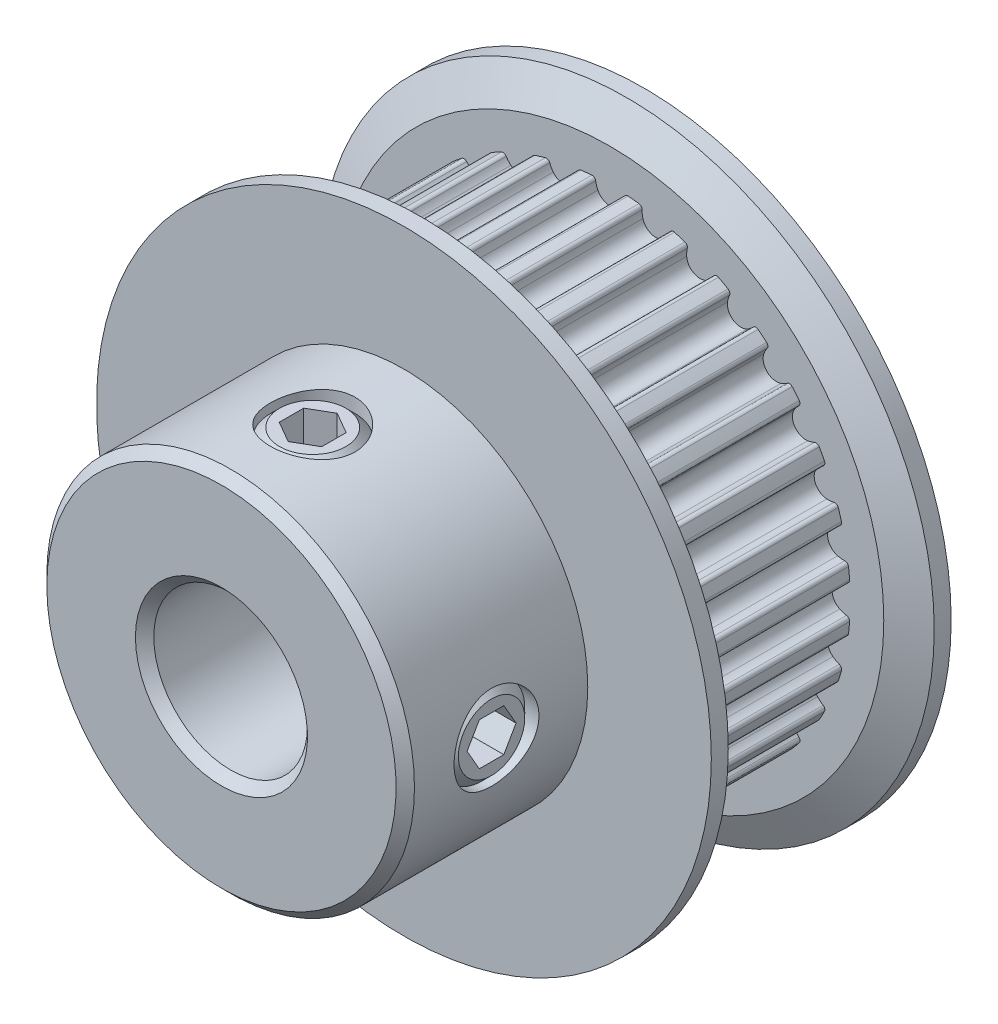
SolidWorks part; units mm, degrees
ref_plane "Front Plane" through (0, 0, 0) normal (0, 0, 1) x (1, 0, 0)
ref_plane "Top Plane" through (0, 0, 0) normal (0, 1, 0) x (1, 0, 0)
ref_plane "Right Plane" through (0, 0, 0) normal (1, 0, 0) x (0, 0, -1)
sketch "Sketch1" plane through (0, 0, 0) normal (0, 0, 1) x (1, 0, 0)
  line L1 (-1.8294, 9.1815) -> (1.8294, 9.1815) construction
  line L4 (0, 0) -> (0, 9.1815) construction
  line L5 (0, 9.1815) -> (0, 13.0713) construction
  line L6 (0, 10.1855) -> (1.9903, 9.9891) construction
  line L7 (1.9903, 9.9891) -> (2.798, 9.8282) construction
  line L8 (1.9903, 9.9891) -> (1.8294, 9.1815) construction
  line L9 (-1.9903, 9.9891) -> (-1.8294, 9.1815) construction
  line L10 (-1.9407, 9.74) -> (-2.5305, 12.7)
  line L11 (-2.5305, 12.7) -> (2.5305, 12.7)
  line L12 (2.5305, 12.7) -> (1.9407, 9.74)
  circle A0 centre (0, 0) radius 10.1855 construction
  circle A1 centre (0, 0) radius 12.7 construction
  circle A2 centre (0, 0) radius 9.9315 construction
  arc A3 (-0.4989, 9.4933) -> (0.4989, 9.4933) centre (0, 9.7365) ccw
  arc A4 (-0.4989, 9.4933) -> (-0.588, 9.7769) centre (0.4, 9.9315) cw
  arc A5 (-1.9407, 9.74) -> (-0.7475, 9.9033) centre (0, 0) cw
  arc A6 (-0.588, 9.7769) -> (-0.7475, 9.9033) centre (-0.7362, 9.7538) ccw
  arc A7 (1.9407, 9.74) -> (0.7475, 9.9033) centre (0, 0) ccw
  arc A8 (0.588, 9.7769) -> (0.7475, 9.9033) centre (0.7362, 9.7538) cw
  arc A9 (0.4989, 9.4933) -> (0.588, 9.7769) centre (-0.4, 9.9315) ccw
  point P6 (0, 20.9083)
  point P11 (0, 10.1855)
  point P13 (0, 12.7)
  point P14 (0, 9.9315)
  dimension "D1" = 7.8371
  dimension "D2" = 2.8858
sketch "Sketch2" plane through (0, 0, 0) normal (1, 0, 0) x (0, 0, -1)
  line L0 (-8.7249, 3.175) -> (8.7249, 3.175)
  line L1 (-8.7249, 3.175) -> (-8.7249, 7.595)
  line L2 (-8.7249, 7.595) -> (-1.1851, 7.595)
  line L3 (-1.1851, 7.595) -> (-1.1851, 12.7)
  line L4 (-1.1851, 12.7) -> (0.2149, 12.7) construction
  line L5 (0.2149, 12.7) -> (0.2149, 9.9315) construction
  line L6 (0.2149, 9.9315) -> (7.3249, 9.9315)
  line L7 (7.3249, 9.9315) -> (7.3249, 12.7) construction
  line L8 (7.3249, 12.7) -> (8.7249, 12.7) construction
  line L9 (8.7249, 12.7) -> (8.7249, 3.175)
  line L10 (-8.7249, 0) -> (8.7249, 0) construction
  line L11 (8.0249, 12.7) -> (7.3249, 11.3157)
  line L12 (0.2149, 11.3157) -> (-0.4851, 12.7)
  line L13 (-1.1851, 12.7) -> (-0.4851, 12.7)
  line L14 (0.2149, 11.3157) -> (0.2149, 9.9315)
  line L15 (7.3249, 9.9315) -> (7.3249, 11.3157)
  line L16 (8.0249, 12.7) -> (8.7249, 12.7)
  arc A0 (0.2149, 11.3157) -> (-0.4851, 12.7) centre (-1.5038, 11.3157) ccw construction
  arc A1 (7.3249, 11.3157) -> (8.0249, 12.7) centre (9.0436, 11.3157) cw construction
  point P12 (0.2149, 11.3157)
  point P14 (-0.4851, 12.7)
  point P20 (7.3249, 11.3157)
  point P21 (8.0249, 12.7)
  point P25 (7.3249, 0)
  point P26 (0.2149, 0)
revolve "Revolve1" add sketch "Sketch2" angle 360 mid plane about L10
sketch "Sketch3" plane through (0, 0, 0) normal (0, 0, 1) x (1, 0, 0)
  line L6 (2.5305, 12.7) -> (-2.5305, 12.7)
  line L7 (1.9407, 9.74) -> (2.5305, 12.7)
  line L8 (-2.5305, 12.7) -> (-1.9407, 9.74)
  line L9 (2.5305, 12.7) -> (-2.5305, 12.7)
  line L10 (1.9407, 9.74) -> (2.5305, 12.7)
  line L11 (-2.5305, 12.7) -> (-1.9407, 9.74)
  arc A8 (1.9407, 9.74) -> (0.7475, 9.9033) centre (0, 0) ccw
  arc A9 (0.7475, 9.9033) -> (0.588, 9.7769) centre (0.7362, 9.7538) ccw
  arc A10 (0.4989, 9.4933) -> (0.588, 9.7769) centre (-0.4, 9.9315) ccw
  arc A11 (-0.4989, 9.4933) -> (0.4989, 9.4933) centre (0, 9.7365) ccw
  arc A12 (-0.588, 9.7769) -> (-0.4989, 9.4933) centre (0.4, 9.9315) ccw
  arc A13 (-0.588, 9.7769) -> (-0.7475, 9.9033) centre (-0.7362, 9.7538) ccw
  arc A14 (-0.7475, 9.9033) -> (-1.9407, 9.74) centre (0, 0) ccw
  arc A15 (1.9407, 9.74) -> (0.7475, 9.9033) centre (0, 0) ccw
  arc A16 (0.7475, 9.9033) -> (0.588, 9.7769) centre (0.7362, 9.7538) ccw
  arc A17 (0.4989, 9.4933) -> (0.588, 9.7769) centre (-0.4, 9.9315) ccw
  arc A18 (-0.4989, 9.4933) -> (0.4989, 9.4933) centre (0, 9.7365) ccw
  arc A19 (-0.588, 9.7769) -> (-0.4989, 9.4933) centre (0.4, 9.9315) ccw
  arc A20 (-0.588, 9.7769) -> (-0.7475, 9.9033) centre (-0.7362, 9.7538) ccw
  arc A21 (-0.7475, 9.9033) -> (-1.9407, 9.74) centre (0, 0) ccw
  dimension "D1" = 0
extrude "Cut-Extrude1" cut sketch "Sketch3" against normal up to vertex (7.3249 mm away) from vertex up to point (0, 9.9315, -7.3249) starting at point (0, 9.9315, -0.2149)
pattern_circular "CirPattern1" count 32 over 360 about axis through (0, 0, 8.7249) along (0, 0, 1) of "Cut-Extrude1"
sketch "Sketch4" plane through (0, 0, 0) normal (1, 0, 0) x (0, -1, 0)
  line L0 (0, -1.1851) -> (0, -8.7249) construction
  line L1 (-7.595, -1.1851) -> (7.595, -1.1851) construction
  line L2 (-7.595, -8.7249) -> (7.595, -8.7249) construction
  circle A0 centre (0, -4.955) radius 1.7526
extrude "Cut-Extrude2" cut sketch "Sketch4" along normal through all
ref_plane "Plane1" through (0, 0, 4.955) normal (0, 0, 1) x (1, 0, 0)
sketch "Sketch5" plane through (0, 0, 4.955) normal (0, 0, 1) x (1, 0, 0)
  line L0 (0, 0.1664) -> (0, 7.595) construction
  line L1 (3.175, -1.3716) -> (3.175, 0)
  line L2 (3.556, -1.7526) -> (7.009, -1.7526)
  line L3 (3.175, 0) -> (7.595, 0) construction
  line L4 (3.175, 0) -> (7.39, 0)
  line L5 (7.39, 0) -> (7.39, -1.3716)
  line L6 (3.556, -1.7526) -> (3.175, -1.3716)
  line L7 (7.39, -1.3716) -> (7.009, -1.7526)
  circle A0 centre (0, 0) radius 7.595 construction
  circle A1 centre (0, 0) radius 3.175 construction
  point P2 (3.175, -1.7526)
  point P11 (7.39, -1.7526)
revolve "Revolve2" add sketch "Sketch5" angle 360 mid plane about L4
sketch "Sketch6" plane through (7.39, 5.3841, 0) normal (-1, 0, 0) x (0, -1, 0)
  line L1 (5.3841, 5.9669) -> (4.5078, 5.4609)
  line L2 (4.5078, 5.4609) -> (4.5078, 4.4491)
  line L3 (4.5078, 4.4491) -> (5.3841, 3.9431)
  line L4 (5.3841, 3.9431) -> (6.2604, 4.4491)
  line L5 (6.2604, 4.4491) -> (6.2604, 5.4609)
  line L6 (6.2604, 5.4609) -> (5.3841, 5.9669)
  circle A0 centre (5.3841, 4.955) radius 0.8763 construction
  dimension "D1" = 1.7526
extrude "Cut-Extrude3" cut sketch "Sketch6" along normal blind 1.3144
pattern_circular "CirPattern2" count 2 over 90 about axis through (0, 0, 8.7249) along (0, 0, 1) of "Cut-Extrude2", "Revolve2", "Cut-Extrude3"
chamfer "Chamfer1" distance 0.3798 angle 45 2 edges at (3.175, 0, 8.7249) (7.595, 0, 8.7249)
ref_axis "Center Axis 1" through (0, 0, -8.7249) along (0, 0, 1)
ref_plane "Contact Plane 1" through (0, 0, 8.7249) normal (0, 0, 1) x (1, 0, 0)
ref_plane "Contact Plane 2" through (0, 0, -8.7249) normal (0, 0, -1) x (-1, 0, 0)
equation "\"D2@Sketch1\" = \"D1@Sketch1\"/2"
equation "\"D1@Sketch6\" = \"Set Screw@Sketch4\" / 2"
equation "\"D1@Cut-Extrude3\" = \"D1@Sketch6\"*.75"
equation "\"D1@Chamfer1\"=\"Hub Dia@Sketch2\"*.025"
